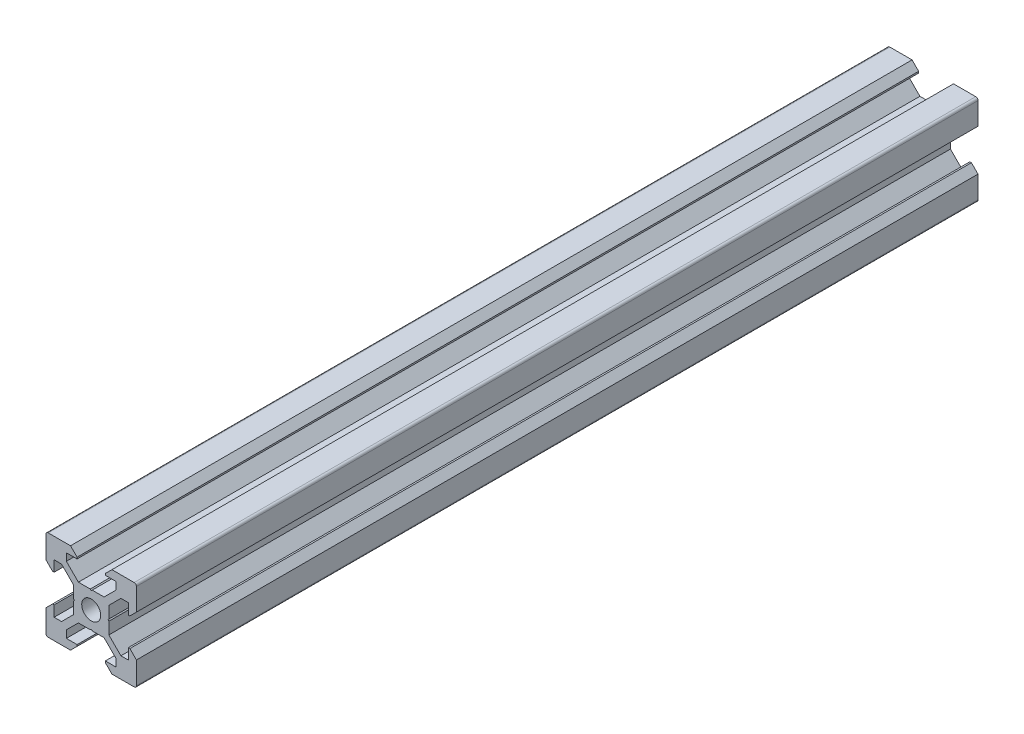
SolidWorks part; units mm, degrees
material "6061-T6 (SS)"
ref_plane "Front Plane" through (0, 0, 0) normal (0, 0, 1) x (1, 0, 0)
ref_plane "Top Plane" through (0, 0, 0) normal (0, 1, 0) x (1, 0, 0)
ref_plane "Right Plane" through (0, 0, 0) normal (1, 0, 0) x (0, 0, -1)
sketch "Sketch1" plane through (0, 0, 0) normal (0, 0, 1) x (1, 0, 0)
  line L1 (9.5, -10) -> (-9.5, -10)
  line L2 (10, -9.5) -> (10, 9.5)
  line L3 (9.5, 10) -> (-9.5, 10)
  line L4 (-10, -9.5) -> (-10, 9.5)
  line L5 (10, -10) -> (-10, 10) construction
  line L6 (10, 10) -> (-10, -10) construction
  circle A0 centre (0, 0) radius 2.1
  arc A1 (-9.5, 10) -> (-10, 9.5) centre (-9.5, 9.5) ccw
  arc A2 (10, 9.5) -> (9.5, 10) centre (9.5, 9.5) ccw
  arc A3 (9.5, -10) -> (10, -9.5) centre (9.5, -9.5) ccw
  arc A4 (-9.5, -10) -> (-10, -9.5) centre (-9.5, -9.5) cw
  point P0 (0, 0)
  line B0 (0, 0) -> (0, 10) construction
  line B1 (0, 3.69) -> (-0.21, 3.9)
  line B2 (-0.21, 3.9) -> (-2.8393, 3.9)
  line B3 (-2.8393, 3.9) -> (-5.5, 6.5607)
  line B4 (-5.5, 6.5607) -> (-5.5, 8.2)
  line B5 (-5.5, 8.2) -> (-3.125, 8.2)
  line B6 (-3.125, 8.2) -> (-3.125, 8.545)
  line B7 (-3.125, 8.545) -> (-4.58, 10)
  line B8 (-4.58, 10) -> (4.58, 10)
  line B9 (0, 0) -> (-5.9132, 5.9132) construction
  line B10 (3.125, 8.545) -> (4.58, 10)
  line B11 (3.125, 8.2) -> (3.125, 8.545)
  line B12 (5.5, 8.2) -> (3.125, 8.2)
  line B13 (5.5, 6.5607) -> (5.5, 8.2)
  line B14 (2.8393, 3.9) -> (5.5, 6.5607)
  line B15 (0.21, 3.9) -> (2.8393, 3.9)
  line B16 (0, 3.69) -> (0.21, 3.9)
  line B17 (0, 0) -> (-10, 0) construction
  line B18 (-3.69, 0) -> (-3.9, -0.21)
  line B19 (-3.9, -0.21) -> (-3.9, -2.8393)
  line B20 (-3.9, -2.8393) -> (-6.5607, -5.5)
  line B21 (-6.5607, -5.5) -> (-8.2, -5.5)
  line B22 (-8.2, -5.5) -> (-8.2, -3.125)
  line B23 (-8.2, -3.125) -> (-8.545, -3.125)
  line B24 (-8.545, -3.125) -> (-10, -4.58)
  line B25 (-10, -4.58) -> (-10, 4.58)
  line B26 (0, 0) -> (-5.9132, -5.9132) construction
  line B27 (-8.545, 3.125) -> (-10, 4.58)
  line B28 (-8.2, 3.125) -> (-8.545, 3.125)
  line B29 (-8.2, 5.5) -> (-8.2, 3.125)
  line B30 (-6.5607, 5.5) -> (-8.2, 5.5)
  line B31 (-3.9, 2.8393) -> (-6.5607, 5.5)
  line B32 (-3.9, 0.21) -> (-3.9, 2.8393)
  line B33 (-3.69, 0) -> (-3.9, 0.21)
  line B34 (0, 0) -> (0, -10) construction
  line B35 (0, -3.69) -> (0.21, -3.9)
  line B36 (0.21, -3.9) -> (2.8393, -3.9)
  line B37 (2.8393, -3.9) -> (5.5, -6.5607)
  line B38 (5.5, -6.5607) -> (5.5, -8.2)
  line B39 (5.5, -8.2) -> (3.125, -8.2)
  line B40 (3.125, -8.2) -> (3.125, -8.545)
  line B41 (3.125, -8.545) -> (4.58, -10)
  line B42 (4.58, -10) -> (-4.58, -10)
  line B43 (0, 0) -> (5.9132, -5.9132) construction
  line B44 (-3.125, -8.545) -> (-4.58, -10)
  line B45 (-3.125, -8.2) -> (-3.125, -8.545)
  line B46 (-5.5, -8.2) -> (-3.125, -8.2)
  line B47 (-5.5, -6.5607) -> (-5.5, -8.2)
  line B48 (-2.8393, -3.9) -> (-5.5, -6.5607)
  line B49 (-0.21, -3.9) -> (-2.8393, -3.9)
  line B50 (0, -3.69) -> (-0.21, -3.9)
  line B51 (0, 0) -> (10, 0) construction
  line B52 (3.69, 0) -> (3.9, 0.21)
  line B53 (3.9, 0.21) -> (3.9, 2.8393)
  line B54 (3.9, 2.8393) -> (6.5607, 5.5)
  line B55 (6.5607, 5.5) -> (8.2, 5.5)
  line B56 (8.2, 5.5) -> (8.2, 3.125)
  line B57 (8.2, 3.125) -> (8.545, 3.125)
  line B58 (8.545, 3.125) -> (10, 4.58)
  line B59 (10, 4.58) -> (10, -4.58)
  line B60 (0, 0) -> (5.9132, 5.9132) construction
  line B61 (8.545, -3.125) -> (10, -4.58)
  line B62 (8.2, -3.125) -> (8.545, -3.125)
  line B63 (8.2, -5.5) -> (8.2, -3.125)
  line B64 (6.5607, -5.5) -> (8.2, -5.5)
  line B65 (3.9, -2.8393) -> (6.5607, -5.5)
  line B66 (3.9, -0.21) -> (3.9, -2.8393)
  line B67 (3.69, 0) -> (3.9, -0.21)
  dimension "D1" = 4.2
  dimension "D3" = 0.5
  dimension "D2" = 20
sketch_block_instance "V Slot 1-4"
sketch_block "V Slot 1" parameters "D1"=10, "D2"=11, "D3"=4.3, "D4"=1.8, "D5"=0.21, "D6"=45, "D7"=9.16, "D8"=1.5, "D9"=6.25
sketch_block_instance "V Slot 1-5"
sketch_block_instance "V Slot 1-6"
sketch_block_instance "V Slot 1-7"
extrude "Boss-Extrude1" add sketch "Sketch1" along normal mid plane 186.1 contours B67 B52 B53 B54 B55 B56 B57 B58 L2 A2 L3 B10 B11 B12 B13 B14 B15 B16 B1 B2 B3 B4 B5 B6 B7 A1 L4 B27 B28 B29 B30 B31 B32 B33 B18 B19 B20 B21 B22 B23 B24 A4 L1 B44 B45 B46 B47 B48 B49 region at (7.04, -9.7172, 0)
